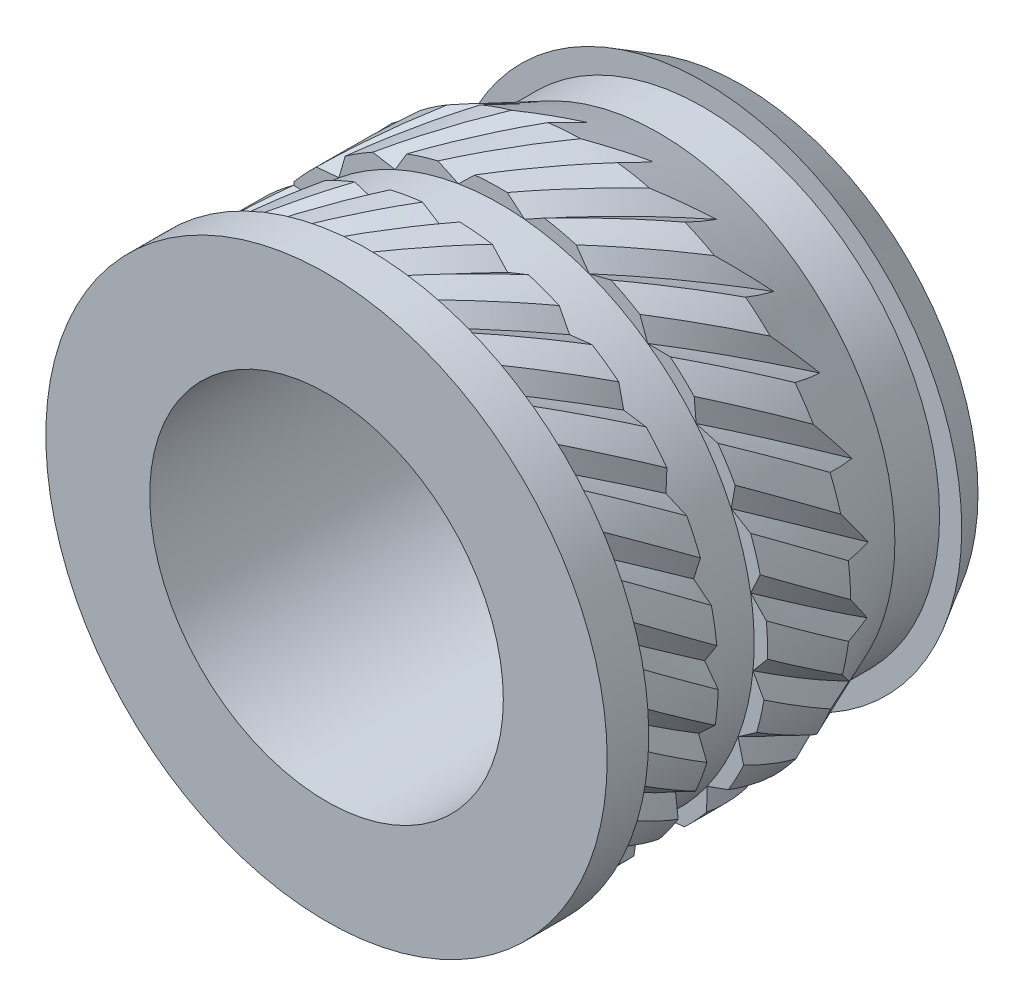
SolidWorks part; units mm, degrees
material "Brass"
ref_plane "Front Plane" through (0, 0, 0) normal (0, 0, 1) x (1, 0, 0)
ref_plane "Top Plane" through (0, 0, 0) normal (0, 1, 0) x (1, 0, 0)
ref_plane "Right Plane" through (0, 0, 0) normal (1, 0, 0) x (0, 0, -1)
sketch "Sketch1" plane through (0, 0, 0) normal (1, 0, 0) x (0, 0, -1)
  line L0 (-2.35, 0) -> (2.35, 0) construction
  line L1 (-2.35, 2) -> (-2.35, 3.175)
  line L2 (-2.35, 3.175) -> (-1.88, 3.175)
  line L3 (-1.88, 3.175) -> (-1.88, 3.0225)
  line L4 (-1.88, 3.0225) -> (-0.94, 3.0225)
  line L5 (-0.94, 3.0225) -> (-0.94, 2.87)
  line L6 (-0.94, 2.87) -> (-0.3832, 2.87)
  line L7 (-0.3832, 2.87) -> (-0.3832, 3.0225)
  line L9 (0.5568, 3.0225) -> (1.41, 2.6691)
  line L13 (1.41, 2.6691) -> (1.9154, 2.6691)
  line L14 (1.9154, 2.6691) -> (1.9154, 2.92)
  line L15 (1.9154, 2.92) -> (2.35, 2.6691)
  line L16 (2.35, 2.6691) -> (2.35, 2)
  line L17 (-2.35, 2.92) -> (2.35, 2.92) construction
  line L18 (2.35, 0) -> (2.35, 2.92) construction
  line L19 (-2.35, 0) -> (-2.35, 3.175) construction
  line L20 (-0.3832, 3.0225) -> (0.5568, 3.0225)
  line L21 (-2.35, 2) -> (2.35, 2)
  line L23 (-3.0063, 2.0758) -> (-2.6563, 1.4696) construction
  line L24 (-2.35, -2.92) -> (2.35, -2.92) construction
  line L25 (-2.6563, 1.4696) -> (-2.3063, 2.0758) construction
  line L26 (-2.3063, 2.0758) -> (-3.0063, 2.0758) construction
  line L27 (-2.9625, 2) -> (-2.35, 2) construction
  line L28 (-2.6563, 2.0758) -> (-2.6563, 2) construction
  line L29 (-2.6563, 2) -> (-2.6563, 1.5453) construction
  line L30 (-2.6563, 1.5453) -> (-2.6563, 1.4696) construction
  line L31 (-2.7, 1.5453) -> (-2.6125, 1.5453)
  line L32 (-2.9844, 2.0379) -> (-2.3281, 2.0379)
  line L33 (-2.6125, 1.5453) -> (-2.3281, 2.0379)
  line L34 (-2.7, 1.5453) -> (-2.9844, 2.0379)
  line L35 (-2.35, 2.87) -> (2.35, 2.87) construction
  line L36 (-2.35, -2.87) -> (2.35, -2.87) construction
  point P36 (-2.6563, 2.0379)
  dimension "Installed Length" = 4.7
  dimension "Dia A" = 6.35
  dimension "Dia B" = 5.84
  dimension "Thread Dia" = 4
  dimension "D6" = 30
  dimension "D8" = 0.94
  dimension "D4" = 22.5
  dimension "Thread Pitch" = 0.7
  dimension "D2" = 0.0875
  dimension "Max Hole Dia" = 5.74
  dimension "Knurling Length" = 3.29
  dimension "D1" = 5.3382
  dimension "D3" = 0.47
ref_plane "Plane1" through (0, 0, 1.88) normal (0, 0, 1) x (1, 0, 0)
sketch "Sketch2" plane through (0, 0, 1.88) normal (0, 0, 1) x (1, 0, 0)
  line L0 (0, 0) -> (0, 3.0225) construction
  line L1 (-0.224, 3.0242) -> (0, 2.87)
  line L2 (0.224, 3.0242) -> (0, 2.87)
  line L3 (-0.2108, 3.0151) -> (0, 0) construction
  line L4 (0.2108, 3.0151) -> (0, 0) construction
  line L5 (0, 0) -> (-0.3945, 2.9966) construction
  line L6 (0, 0) -> (0.3945, 2.9966) construction
  line L7 (0, 0) -> (2.1372, 2.1372) construction
  line L8 (0, 0) -> (0, -2.0758) construction
  line L9 (0, 0) -> (1.0379, -1.7977) construction
  circle A0 centre (0, 0) radius 2.87 construction
  circle A1 centre (0, 0) radius 3.0225 construction
  circle A3 centre (0, 0) radius 2.0758
  arc A4 (-0.224, 3.0242) -> (0.224, 3.0242) centre (0, 0) cw
  dimension "Knurl Angle" = 8
  dimension "Pattern Angle" = 15
  dimension "Helix Angle" = 45
  dimension "D1" = 30
sketch "Sketch3" plane through (0, 0, 0) normal (1, 0, 0) x (0, 0, -1)
  line L0 (-2.35, 2) -> (-2.35, 3.175) construction
  line L1 (-2.35, 3.175) -> (-1.88, 3.175) construction
  line L2 (-1.88, 3.175) -> (-1.88, 3.0225) construction
  line L3 (-1.88, 3.0225) -> (-0.94, 3.0225) construction
  line L4 (-0.94, 3.0225) -> (-0.94, 2.87) construction
  line L5 (-0.94, 2.87) -> (-0.3832, 2.87) construction
  line L6 (-0.3832, 2.87) -> (-0.3832, 3.0225) construction
  line L8 (0.5568, 3.0225) -> (1.41, 2.6691) construction
  line L12 (1.41, 2.6691) -> (1.9154, 2.6691) construction
  line L13 (1.9154, 2.6691) -> (1.9154, 2.92) construction
  line L14 (1.9154, 2.92) -> (2.35, 2.6691) construction
  line L15 (2.35, 2.6691) -> (2.35, 2) construction
  line L16 (-2.35, 2) -> (2.35, 2) construction
  line L17 (-2.35, 2) -> (-2.35, 3.175)
  line L18 (-2.35, 3.175) -> (-1.88, 3.175)
  line L19 (-1.88, 3.175) -> (-1.88, 3.0225)
  line L20 (-1.88, 3.0225) -> (-0.94, 3.0225)
  line L21 (-0.94, 3.0225) -> (-0.94, 2.87)
  line L22 (-0.94, 2.87) -> (-0.3832, 2.87)
  line L23 (-0.3832, 2.87) -> (-0.3832, 3.0225)
  line L25 (0.5568, 3.0225) -> (1.41, 2.6691)
  line L29 (1.41, 2.6691) -> (1.9154, 2.6691)
  line L30 (1.9154, 2.6691) -> (1.9154, 2.92)
  line L31 (1.9154, 2.92) -> (2.35, 2.6691)
  line L32 (2.35, 2.6691) -> (2.35, 2)
  line L33 (-2.35, 2) -> (2.35, 2)
  line L34 (-0.3832, 3.0225) -> (0.5568, 3.0225) construction
  line L35 (-0.3832, 3.0225) -> (0.5568, 3.0225)
revolve "Revolve1" add sketch "Sketch3" angle 360 about L0
sketch "Sketch4" plane through (0, 0, 1.88) normal (0, 0, 1) x (1, 0, 0)
  circle A2 centre (0, 0) radius 3.0225 construction
  circle A3 centre (0, 0) radius 3.0225
sketch "Sketch6" [suppressed] plane through (0, 0, 2.35) normal (0, 0, 1) x (1, 0, 0)
  circle A0 centre (0, 0) radius 2
curve "Helix/Spiral2" [suppressed] pitch 0.7 height 5.4 turns 7.7143
sketch "Sketch7" [suppressed] plane through (0, 0, 0) normal (1, 0, 0) x (0, 0, -1)
  line L0 (-2.7, 1.5453) -> (-2.6125, 1.5453) construction
  line L1 (-2.7, 1.5453) -> (-2.9844, 2.0379) construction
  line L2 (-2.9844, 2.0379) -> (-2.3281, 2.0379) construction
  line L3 (-2.6125, 1.5453) -> (-2.3281, 2.0379) construction
  line L4 (-2.7, 1.5453) -> (-2.6125, 1.5453)
  line L5 (-2.7, 1.5453) -> (-2.9844, 2.0379)
  line L6 (-2.9844, 2.0379) -> (-2.3281, 2.0379)
  line L7 (-2.6125, 1.5453) -> (-2.3281, 2.0379)
sweep "Sweep1" [suppressed] add profiles "Sketch7" path "Helix/Spiral2"
sketch "Sketch8" [suppressed] plane through (0, 0, 2.35) normal (0, 0, 1) x (1, 0, 0)
  circle A0 centre (0, 0) radius 2.0758
extrude "Cut-Extrude1" [suppressed] cut sketch "Sketch8" against normal through all draft 45 and the other way through all
mirror "Mirror1" [suppressed] about plane through (0, 0, 0) normal (0, 0, 1)
curve "Helix/Spiral1" pitch 26.32 height 3.29 radius 3.0225 centre (0, 0, 1.88) axis (0, 0, -1) start towards (0, 1, 0)
sketch "Sketch5" plane through (0, 0, 1.88) normal (0, 0, 1) x (1, 0, 0)
  line L0 (-0.224, 3.0242) -> (0, 2.87) construction
  line L1 (0.224, 3.0242) -> (0, 2.87) construction
  line L2 (-0.224, 3.0242) -> (0, 2.87)
  line L3 (0.224, 3.0242) -> (0, 2.87)
  arc A2 (0.224, 3.0242) -> (-0.224, 3.0242) centre (0, 0) ccw construction
  arc A3 (0.224, 3.0242) -> (-0.224, 3.0242) centre (0, 0) ccw
sweep "Cut-Sweep1" cut profiles "Sketch5" path "Helix/Spiral1" align with end faces yes
pattern_circular "CirPattern1" count 24 over 360 about axis through (0, 0, 2.35) along (0, 0, -1) of "Cut-Sweep1"
equation "\"D8@Sketch1\"=\"Installed Length@Sketch1\" * .2"
equation "\"D4@Helix/Spiral1\"=\"Knurling Length@Sketch1\"*(360/\"Helix Angle@Sketch2\")"
equation "\"D3@Helix/Spiral1\"=\"Knurling Length@Sketch1\""
equation "\"D1@CirPattern1\"=\"D3@CirPattern1\"/\"Pattern Angle@Sketch2\""
equation "\"D2@Sketch1\" = \"Thread Pitch@Sketch1\" / 8"
equation "\"D4@Helix/Spiral2\"=\"Thread Pitch@Sketch1\""
equation "\"D3@Helix/Spiral2\" = \"Installed Length@Sketch1\" + \"Thread Pitch@Sketch1\""
equation "\"Knurling Length@Sketch1\"=\"Installed Length@Sketch1\" * .7"
equation "\"D1@Sketch1\"=\"Max Hole Dia@Sketch1\"*.93"
equation "\"D3@Sketch1\"=\"Installed Length@Sketch1\"*.1"
